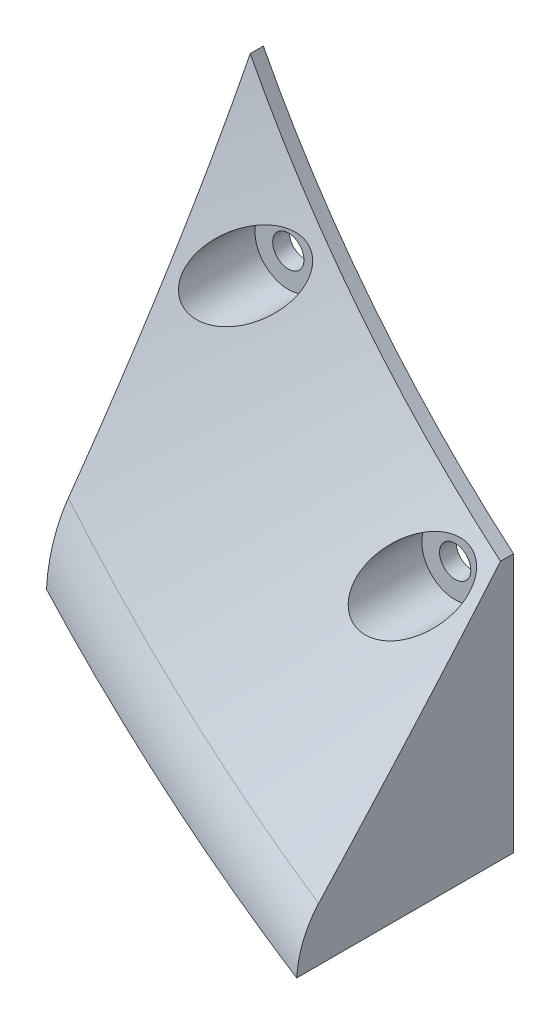
SolidWorks part; units mm, degrees
material "6061 Alloy"
ref_plane "Front Plane" through (0, 0, 0) normal (0, 0, 1) x (1, 0, 0)
ref_plane "Top Plane" through (0, 0, 0) normal (0, 1, 0) x (1, 0, 0)
ref_plane "Right Plane" through (0, 0, 0) normal (1, 0, 0) x (0, 0, -1)
sketch "Sketch1" plane through (0, 0, 0) normal (0, 0, 1) x (1, 0, 0)
  line L1 (-140.9655, 145.0225) -> (-102.8655, 145.0225)
  line L2 (-140.9655, 145.0225) -> (-140.9655, -145.0225)
  line L3 (-140.9655, -145.0225) -> (-102.8655, -145.0225)
  line L4 (-102.8655, 145.0225) -> (-102.8655, -145.0225)
  line L5 (-140.9655, 145.0225) -> (-102.8655, -145.0225) construction
  line L6 (-140.9655, -145.0225) -> (-102.8655, 145.0225) construction
  line L7 (-140.9655, 31.75) -> (140.9655, 31.75)
  line L8 (-140.9655, 31.75) -> (-140.9655, -31.75)
  line L9 (-140.9655, -31.75) -> (140.9655, -31.75)
  line L10 (140.9655, 31.75) -> (140.9655, -31.75)
  line L11 (-140.9655, 31.75) -> (140.9655, -31.75) construction
  line L12 (-140.9655, -31.75) -> (140.9655, 31.75) construction
  line L13 (102.8655, 145.0225) -> (140.9655, 145.0225)
  line L14 (102.8655, 145.0225) -> (102.8655, -145.0225)
  line L15 (102.8655, -145.0225) -> (140.9655, -145.0225)
  line L16 (140.9655, 145.0225) -> (140.9655, -145.0225)
  line L17 (102.8655, 145.0225) -> (140.9655, -145.0225) construction
  line L18 (102.8655, -145.0225) -> (140.9655, 145.0225) construction
  line L19 (-140.9655, -31.75) -> (140.9655, -31.75)
  line L20 (-140.9655, -31.75) -> (-140.9655, -69.85)
  line L21 (-140.9655, -69.85) -> (140.9655, -69.85)
  line L22 (140.9655, -31.75) -> (140.9655, -69.85)
  circle A0 centre (0, 0) radius 177.8
  circle A7 centre (0, -38.1) radius 25.4 construction
  circle A8 centre (-25.4, -38.1) radius 2.3813
  circle A9 centre (25.4, -38.1) radius 2.3813
  circle A10 centre (0, -38.1) radius 2.3812
  point P3 (-121.9155, 0)
  point P12 (121.9155, 0)
  dimension "D1" = 355.6
  dimension "D5" = 50.8
  dimension "D6" = 38.1
  dimension "D7" = 281.9311
  dimension "D10" = 4.7625
  dimension "D8" = 4.7625
  dimension "D9" = 4.7625
  dimension "D2" = 38.1
  dimension "D3" = 38.1
  dimension "D4" = 63.5
  dimension "D12" = 38.1
extrude "Boss-Extrude1" add sketch "Sketch1" along normal blind 3.175 contours L4 A0 L2 L7 | L2 L9 L4 L7 | L14 L7 L4 L9 A8 | L2 A0 L4 L9 | L16 A0 L14 L7 | L7 L14 L9 L10 | L14 A0 L16 L9 | L19 A10 L9 L4 L21 L14 A9 A8 | L2 L21 L4 L9 | L14 L21 L16 L9 region at (-120.723, 80.7079, 0) region at (0, 0, 0) region at (-121.9155, 0, 0) region at (120.723, 80.7079, 0) region at (-119.9486, -100.1295, 0) region at (0, -50.8872, 0) region at (-121.9155, -50.8, 0) region at (121.9155, 0, 0) region at (121.9155, -50.8, 0) region at (119.9486, -100.1295, 0)
sketch "Sketch2" plane through (0, 0, 3.175) normal (0, 0, 1) x (1, 0, 0)
  line L0 (-140.9655, -103.066) -> (-140.9655, -108.3585)
  line L1 (-140.9655, 108.3585) -> (-140.9655, -108.3585) construction
  line L2 (-102.8655, -141.1119) -> (-102.8655, -145.0225)
  line L3 (102.8655, -141.1119) -> (102.8655, -145.0225)
  line L4 (102.8655, -69.85) -> (102.8655, -145.0225) construction
  line L5 (140.9655, -103.066) -> (140.9655, -108.3585)
  line L6 (140.9655, 108.3585) -> (140.9655, -108.3585) construction
  line L7 (-102.8655, -69.85) -> (-102.8655, -145.0225) construction
  circle A0 centre (0, 0) radius 177.8
  circle A1 centre (0, 0) radius 174.625
  line M3 (-140.9655, 108.3585) -> (-140.9655, -108.3585)
  arc M4 (-140.9655, -108.3585) -> (-102.8655, -145.0225) centre (0, 0) ccw
  line M5 (-102.8655, -145.0225) -> (-102.8655, -69.85)
  line M7 (102.8655, -69.85) -> (102.8655, -145.0225)
  arc M8 (102.8655, -145.0225) -> (140.9655, -108.3585) centre (0, 0) ccw
  line M9 (140.9655, -108.3585) -> (140.9655, 108.3585)
  dimension "D1" = 355.6
  dimension "D2" = 349.25
extrude "Boss-Extrude2" add sketch "Sketch2" along normal blind 50.8 contours A1 M3 M4 M5 | A1 M7 M8 M9 region at (-122.8631, -125.3578, 3.175) region at (122.8631, -125.3578, 3.175)
sketch "Sketch3" plane through (0, 0, 3.175) normal (0, 0, 1) x (1, 0, 0)
  circle A0 centre (0, 0) radius 174.625
  circle A1 centre (0, 0) radius 203.8293
  dimension "D1" = 349.25
extrude "Cut-Extrude1" cut sketch "Sketch3" along normal through all and the other way through all
sketch "Sketch5" plane through (0, 0, 3.175) normal (0, 0, 1) x (1, 0, 0)
  line L0 (0, 165.1) -> (0, -165.1) construction
  line L1 (102.8655, -69.85) -> (102.8655, -141.1119) construction
  circle A0 centre (0, 0) radius 165.1 construction
  circle A1 centre (134.6155, -95.5859) radius 2.3813
  circle A2 centre (109.2155, -123.8143) radius 2.3813
  circle A3 centre (-134.6155, -95.5859) radius 2.3813
  circle A4 centre (-109.2155, -123.8143) radius 2.3813
  arc A5 (140.9655, 103.066) -> (102.8655, 141.1119) centre (0, 0) ccw construction
  dimension "D1" = 330.2
  dimension "D3" = 4.7625
  dimension "D4" = 4.7625
  dimension "D2" = 25.4
  dimension "D5" = 6.35
extrude "Cut-Extrude3" cut sketch "Sketch5" against normal through all
sketch "Sketch6" plane through (0, 0, 3.175) normal (0, 0, 1) x (1, 0, 0)
  line L0 (-102.8655, 141.1119) -> (-102.8655, 31.75) construction
  line L1 (-102.8655, 90.3119) -> (102.8655, 90.3119)
  line L2 (-102.8655, 90.3119) -> (-102.8655, 64.9119)
  line L3 (-102.8655, 64.9119) -> (102.8655, 64.9119)
  line L4 (102.8655, 90.3119) -> (102.8655, 64.9119)
  line L5 (102.8655, 141.1119) -> (102.8655, 31.75) construction
  dimension "D1" = 25.4
  dimension "D2" = 50.8
extrude "Boss-Extrude3" add sketch "Sketch6" against normal blind 3.175
sketch "Sketch7" plane through (0, 0, 3.175) normal (0, 0, 1) x (1, 0, 0)
  line L0 (102.8655, 90.3119) -> (-102.8655, 90.3119) construction
  line L1 (-157.8266, 90.3119) -> (153.0605, 90.3119)
  line L2 (-157.8266, 90.3119) -> (-157.8266, 162.3702)
  line L3 (-157.8266, 162.3702) -> (153.0605, 162.3702)
  line L4 (153.0605, 90.3119) -> (153.0605, 162.3702)
extrude "Cut-Extrude4" [suppressed] cut sketch "Sketch7" against normal through all
sketch "Sketch8" plane through (0, 0, 3.175) normal (0, 0, 1) x (1, 0, 0)
  circle A0 centre (0, -38.1) radius 38.1 construction
  circle A1 centre (-38.1, -38.1) radius 2.3812
  circle A2 centre (0, -38.1) radius 50.8 construction
  circle A3 centre (-50.8, -38.1) radius 2.3812
  circle A4 centre (0, -38.1) radius 12.7 construction
  circle A5 centre (12.7, -38.1) radius 2.3812
  circle A6 centre (-12.7, -38.1) radius 2.3812
  dimension "D1" = 76.2
  dimension "D2" = 4.7625
  dimension "D3" = 101.6
  dimension "D4" = 4.7625
  dimension "D5" = 25.4
  dimension "D6" = 4.7625
  dimension "D7" = 4.7625
extrude "Cut-Extrude5" cut sketch "Sketch8" against normal through all
sketch "Sketch9" plane through (0, 0, 3.175) normal (0, 0, 1) x (1, 0, 0)
  line L0 (102.8655, -69.85) -> (102.8655, -141.1119) construction
  line L1 (-102.8655, -69.85) -> (102.8655, -69.85)
  line L2 (-102.8655, -69.85) -> (-102.8655, -107.95)
  line L3 (-102.8655, -107.95) -> (102.8655, -107.95)
  line L4 (102.8655, -69.85) -> (102.8655, -107.95)
  dimension "D1" = 38.1
extrude "Boss-Extrude4" add sketch "Sketch9" against normal blind 3.175
sketch "Sketch10" plane through (0, 0, 3.175) normal (0, 0, 1) x (1, 0, 0)
  circle A0 centre (0, -76.2) radius 6.35
  circle A1 centre (0, -38.1) radius 2.3812 construction
  circle A2 centre (0, -76.2) radius 25.4 construction
  circle A3 centre (0, -76.2) radius 38.1 construction
  circle A4 centre (-25.4, -76.2) radius 2.3813
  circle A5 centre (-38.1, -76.2) radius 2.3812
  circle A6 centre (25.4, -76.2) radius 2.3813
  dimension "D1" = 38.1
  dimension "D2" = 12.7
  dimension "D3" = 50.8
  dimension "D4" = 76.2
  dimension "D5" = 4.7625
  dimension "D6" = 4.7625
  dimension "D7" = 4.7625
extrude "Cut-Extrude6" cut sketch "Sketch10" against normal through all
sketch "Sketch11" plane through (0, 0, 3.175) normal (0, 0, 1) x (1, 0, 0)
  line L0 (-102.8655, -107.95) -> (102.8655, -107.95) construction
  line L1 (-26.6655, -107.95) -> (26.6655, -107.95)
  line L2 (-26.6655, -107.95) -> (-26.6655, -139.7)
  line L3 (-26.6655, -139.7) -> (26.6655, -139.7)
  line L4 (26.6655, -107.95) -> (26.6655, -139.7)
  line L5 (-102.8655, -107.95) -> (-102.8655, -141.1119) construction
  line L6 (102.8655, -107.95) -> (102.8655, -141.1119) construction
  dimension "D1" = 31.75
  dimension "D2" = 76.2
  dimension "D3" = 76.2
extrude "Boss-Extrude5" add sketch "Sketch11" against normal blind 3.175
fillet "Fillet1" radius 10.16 4 edges at (26.6655, -107.95, 1.5875) (-26.6655, -107.95, 1.5875) (-26.6655, -139.7, 1.5875) (26.6655, -139.7, 1.5875)
sketch "Sketch12" plane through (0, 0, 3.175) normal (0, 0, 1) x (1, 0, 0)
  line L1 (-12.7, -63.5) -> (12.7, -63.5) construction
  line L2 (-12.7, -63.5) -> (-12.7, -88.9) construction
  line L3 (-12.7, -88.9) -> (12.7, -88.9) construction
  line L4 (12.7, -63.5) -> (12.7, -88.9) construction
  circle A0 centre (-25.4, -76.2) radius 6.35
  circle A1 centre (25.4, -76.2) radius 6.35
  circle A2 centre (0, -76.2) radius 6.35 construction
  circle A3 centre (-8.6678, -67.5323) radius 2.3812
  circle A7 centre (8.6677, -67.5322) radius 2.3813
  circle A8 centre (8.6678, -84.8677) radius 2.3812
  circle A9 centre (-8.6677, -84.8677) radius 2.3812
  point P23 (0, -76.2)
  point P24 (0, -76.2)
  dimension "D1" = 12.7
  dimension "D2" = 12.7
  dimension "D7" = 4.0323
  dimension "D9" = 4.7625
  dimension "D3" = 12.7
  dimension "D4" = 25.4
  dimension "D5" = 12.7
  dimension "D6" = 25.4
  dimension "D8" = 4.0323
  dimension "D10" = 4
extrude "Cut-Extrude7" cut sketch "Sketch12" against normal through all
fillet "Fillet2" radius 2.54 2 edges at (102.8655, 141.1119, 1.5875) (-102.8655, 141.1119, 1.5875)
sketch "Sketch13" plane through (0, 0, 3.175) normal (0, 0, 1) x (1, 0, 0)
  line L0 (-140.9655, -16.1069) -> (140.9655, -16.1069) construction
  line L1 (-140.9655, 103.066) -> (-140.9655, -103.066) construction
  line L2 (140.9655, 103.066) -> (140.9655, -103.066) construction
  text T0 "7042" font "Aero" height 25.4
extrude "Cut-Extrude8" cut sketch "Sketch13" against normal through all
sketch "Sketch14" plane through (0, 0, 3.175) normal (0, 0, 1) x (1, 0, 0)
  line L1 (-12.3972, 11.8715) -> (-9.6379, 11.8715)
  line L2 (-12.3972, 11.8715) -> (-12.3972, 3.9079)
  line L3 (-12.3972, 3.9079) -> (-9.6379, 3.9079)
  line L4 (-9.6379, 11.8715) -> (-9.6379, 3.9079)
  line L5 (-16.0587, -11.8105) -> (-13.5317, -11.8105)
  line L6 (-16.0587, -11.8105) -> (-16.0587, -17.7494)
  line L7 (-16.0587, -17.7494) -> (-13.5317, -17.7494)
  line L8 (-13.5317, -11.8105) -> (-13.5317, -17.7494)
extrude "Boss-Extrude6" add sketch "Sketch14" against normal blind 3.175
fillet "Fillet3" radius 2.54 6 edges at (-102.8655, 90.3119, 1.5875) (102.8655, 90.3119, 1.5875) (102.8655, 31.75, 1.5875) (102.8655, 64.9119, 1.5875) (-102.8655, 31.75, 1.5875) (-102.8655, 64.9119, 1.5875)
sketch "Sketch15" plane through (0, 0, 3.175) normal (0, 0, 1) x (1, 0, 0)
  line L0 (-140.9655, -30.7998) -> (-140.9655, -128.1365)
  line L1 (-140.9655, 103.066) -> (-140.9655, -103.066) construction
  line L2 (140.9655, -44.4978) -> (140.9655, -128.1365)
  line L3 (140.9655, 103.066) -> (140.9655, -103.066) construction
  line L4 (-102.8655, -107.95) -> (-102.8655, -160.34)
  line L5 (102.8655, -107.95) -> (102.8655, -160.34)
  circle A0 centre (0, 0) radius 158.75
  circle A1 centre (0, 0) radius 190.5
  circle A2 centre (-134.6155, -95.5859) radius 2.3813
  circle A3 centre (-109.2155, -123.8143) radius 2.3812
  circle A4 centre (109.2155, -123.8143) radius 2.3813
  circle A5 centre (109.2155, -123.8143) radius 2.3813 construction
  circle A6 centre (134.6155, -95.5859) radius 2.3813
  dimension "D1" = 317.5
  dimension "D2" = 381
extrude "Boss-Extrude7" add sketch "Sketch15" along normal blind 33.02 contours L0 A1 L4 A0 | L5 A1 L2 A0 region at (-122.9806, -122.07, 3.175) region at (122.9806, -122.07, 3.175)
sketch "Sketch16" plane through (0, 0, 3.175) normal (0, 0, 1) x (1, 0, 0)
  line L1 (-160.8587, 42.3801) -> (207.6811, 42.3801)
  line L2 (-160.8587, 42.3801) -> (-160.8587, 189.4949)
  line L3 (-160.8587, 189.4949) -> (207.6811, 189.4949)
  line L4 (207.6811, 42.3801) -> (207.6811, 189.4949)
  circle A0 centre (0, 0) radius 227.7547
  point P7 (207.6811, 189.4949)
extrude "Cut-Extrude9" cut sketch "Sketch16" against normal through all contours L1 A0 | L1 A0 | A0 L1 L4 L3 L2 region at (15.0013, 112.5626, 3.175) region at (-7.1756, -66.5524, 3.175)
sketch "Sketch17" plane through (0, 0, 36.195) normal (0, 0, 1) x (1, 0, 0)
  circle A0 centre (124.015, -121.333) radius 87.1955
extrude "Cut-Extrude10" cut sketch "Sketch17" against normal through all
chamfer "Chamfer1" distance 27.94 angle 48 1 edges at (-124.2463, -98.8151, 36.195) first distance on face at (-106.8343, -123.8143, 36.195)
sketch "Sketch18" plane through (0, 0, 3.175) normal (0, 0, -1) x (-1, 0, 0)
  circle A0 centre (0, 0) radius 171.45 construction
  circle A2 centre (134.6155, -95.5859) radius 5.08
  circle A6 centre (109.2155, -123.8143) radius 5.08
  circle A7 centre (109.2155, -123.8143) radius 2.3813 construction
  dimension "D1" = 342.9
  dimension "D2" = 10.16
  dimension "D3" = 10.16
extrude "Cut-Extrude12" cut sketch "Sketch18" against normal blind 33.02 from offset 2.54 offset against normal yes
fillet "Fillet4" radius 10.16 1 edges at (-123.0536, -140.3958, 36.195)
